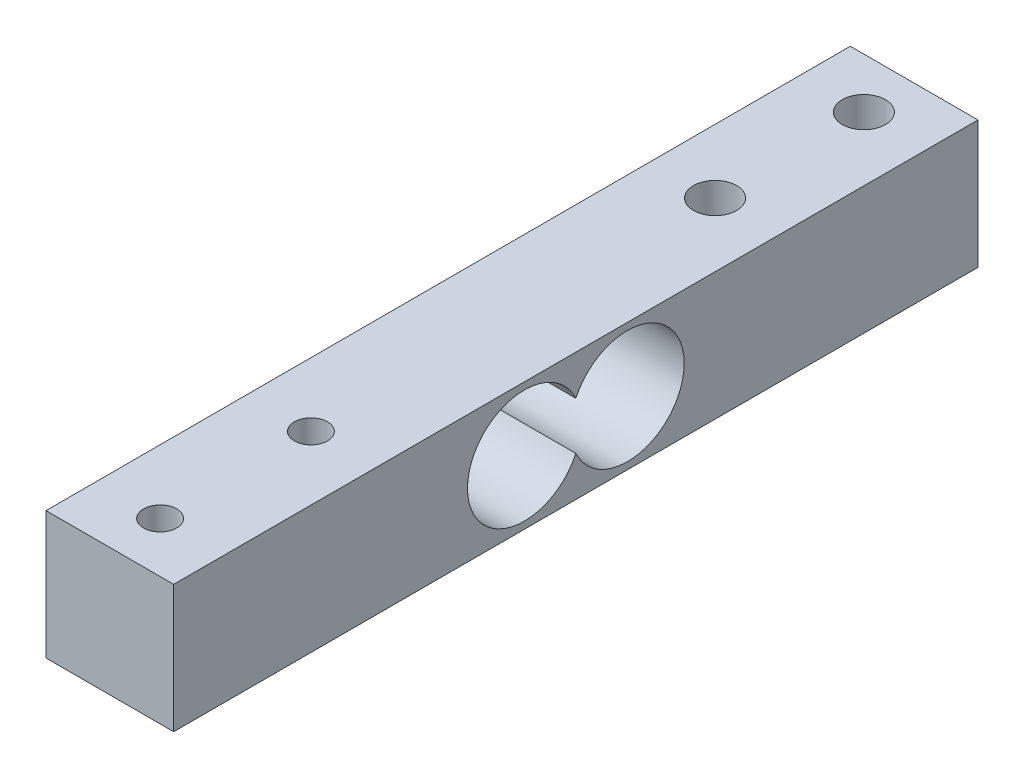
SolidWorks part; units mm, degrees
ref_plane "Front Plane" through (0, 0, 0) normal (0, 0, 1) x (1, 0, 0)
ref_plane "Top Plane" through (0, 0, 0) normal (0, 1, 0) x (1, 0, 0)
ref_plane "Right Plane" through (0, 0, 0) normal (1, 0, 0) x (0, 0, -1)
sketch "Sketch1" plane through (0, 0, 0) normal (0, 0, 1) x (1, 0, 0)
  line L1 (-6.35, -6.35) -> (6.35, -6.35)
  line L2 (-6.35, -6.35) -> (-6.35, 6.35)
  line L3 (-6.35, 6.35) -> (6.35, 6.35)
  line L4 (6.35, -6.35) -> (6.35, 6.35)
  point P8 (0, -6.35)
  point P9 (-6.35, 0)
  dimension "D1" = 12.7
  dimension "D2" = 12.7
extrude "Boss-Extrude1" add sketch "Sketch1" along normal blind 80
sketch "Sketch2" plane through (6.35, 0, 0) normal (1, 0, 0) x (0, 0, -1)
  line L0 (-80, -6.35) -> (-80, 6.35) construction
  line L1 (-45.1266, 0) -> (-34.8734, 0) construction
  line L2 (-80, -6.35) -> (0, -6.35) construction
  arc A0 (-40, 2.375) -> (-40, -2.375) centre (-45.1266, 0) ccw
  arc A1 (-40, -2.375) -> (-40, 2.375) centre (-34.8734, 0) ccw
  point P7 (-80, 0)
  point P9 (-40, -6.35)
  point P10 (-40, 0)
  dimension "D1" = 11.3
  dimension "D2" = 4.75
extrude "Cut-Extrude1" cut sketch "Sketch2" against normal through all
sketch "Sketch3" plane through (0, 6.35, 0) normal (0, 1, 0) x (1, 0, 0)
  circle A0 centre (0, -5) radius 2.15
  circle A1 centre (0, -19.8) radius 2.15
  dimension "D3" = 4.3
  dimension "D1" = 14.8
  dimension "D2" = 5
extrude "Cut-Extrude2" cut sketch "Sketch3" against normal through all
sketch "Sketch4" plane through (0, 6.35, 0) normal (0, 1, 0) x (1, 0, 0)
  line L0 (6.35, -80) -> (-6.35, -80) construction
  circle A0 centre (0, -75) radius 1.65
  circle A1 centre (0, -60) radius 1.65
  point P8 (0, -80)
  dimension "D3" = 3.3
  dimension "D1" = 5
  dimension "D2" = 15
extrude "Cut-Extrude3" cut sketch "Sketch4" against normal through all
sketch "Sketch8" plane through (0, -6.35, 0) normal (0, -1, 0) x (1, 0, 0)
  line L0 (-6.35, 26) -> (6.35, 26)
  line L1 (-6.35, 80) -> (-6.35, 0) construction
  line L2 (6.35, 80) -> (6.35, 0) construction
  line L3 (6.985, 0) -> (-6.985, 0) construction
  line L4 (-6.35, 54) -> (6.35, 54)
  line L5 (-6.35, 80) -> (6.35, 80) construction
  dimension "D1" = 26
  dimension "D2" = 26
split line "Split Line4"
sketch "Sketch9" plane through (0, 0, 0) normal (0, 1, 0) x (1, 0, 0)
  line L0 (-6.35, -67.5) -> (6.35, -67.5) construction
  line L1 (-6.35, -80) -> (-6.35, 0) construction
  line L2 (6.35, -80) -> (6.35, 0) construction
  line L3 (6.35, -80) -> (-6.35, -80) construction
  dimension "D1" = 12.5
ref_axis "Axis1" through (-6.35, 0, 67.5) along (1, 0, 0)
ref_axis "Axis2" through (0, 0, -4) along (0, 0, 1)
